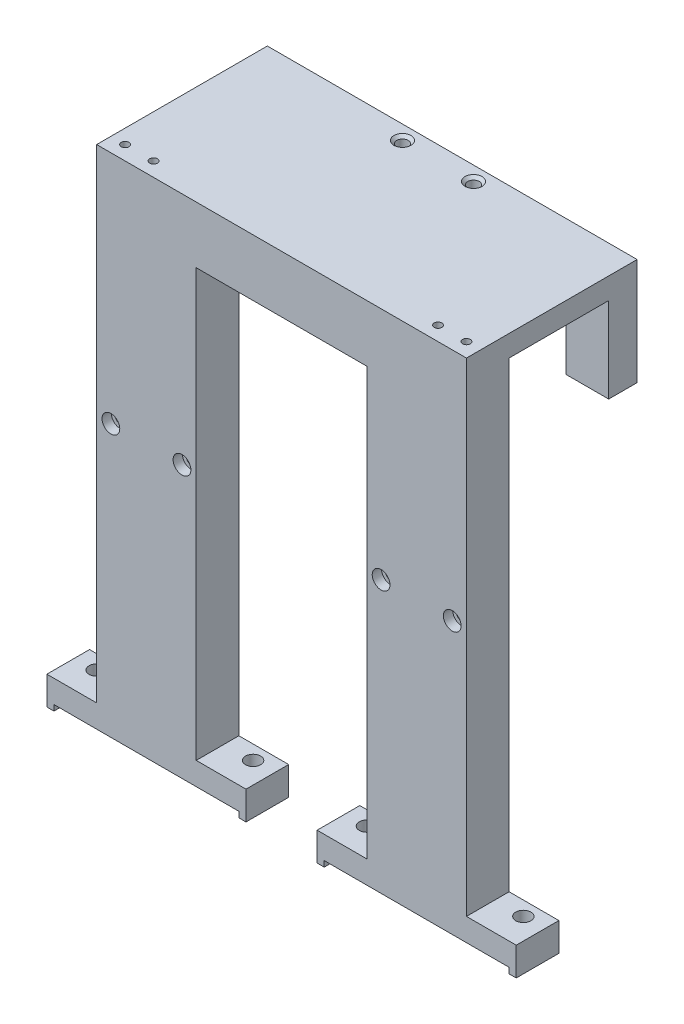
SolidWorks part; units mm, degrees
material "6061 Alloy"
ref_plane "Front Plane" through (0, 0, 0) normal (0, 0, 1) x (1, 0, 0)
ref_plane "Top Plane" through (0, 0, 0) normal (0, 1, 0) x (1, 0, 0)
ref_plane "Right Plane" through (0, 0, 0) normal (1, 0, 0) x (0, 0, -1)
sketch "Sketch1" plane through (0, 0, 0) normal (0, 0, 1) x (1, 0, 0)
  line L1 (-82.55, -114.3) -> (82.55, -114.3)
  line L2 (-82.55, -114.3) -> (-82.55, 114.3)
  line L3 (-82.55, 114.3) -> (82.55, 114.3)
  line L4 (82.55, -114.3) -> (82.55, 114.3)
  line L5 (-82.55, -114.3) -> (82.55, 114.3) construction
  line L6 (-82.55, 114.3) -> (82.55, -114.3) construction
  point P0 (0, 0)
  dimension "D1" = 228.6
  dimension "D2" = 165.1
extrude "Boss-Extrude1" add sketch "Sketch1" along normal blind 19.05
sketch "Sketch2" plane through (0, 0, 19.05) normal (0, 0, 1) x (1, 0, 0)
  line L0 (-82.55, -114.3) -> (82.55, -114.3) construction
  line L1 (-38.1, -114.3) -> (38.1, -114.3)
  line L2 (-38.1, -114.3) -> (-38.1, 88.9)
  line L3 (-38.1, 88.9) -> (38.1, 88.9)
  line L4 (38.1, -114.3) -> (38.1, 88.9)
  line L5 (-82.55, 114.3) -> (-82.55, -114.3) construction
  dimension "D1" = 203.2
  dimension "D2" = 76.2
  dimension "D3" = 44.45
extrude "Cut-Extrude1" cut sketch "Sketch2" against normal through all
sketch "Sketch3" plane through (0, 0, 0) normal (0, 0, -1) x (-1, 0, 0)
  line L0 (82.55, 114.3) -> (82.55, -114.3) construction
  line L1 (-82.55, 114.3) -> (82.55, 114.3)
  line L2 (-82.55, 114.3) -> (-82.55, 104.775)
  line L3 (-82.55, 104.775) -> (82.55, 104.775)
  line L4 (82.55, 114.3) -> (82.55, 104.775)
  dimension "D1" = 9.525
extrude "Boss-Extrude2" add sketch "Sketch3" along normal blind 57.15
sketch "Sketch4" plane through (0, 0, -57.15) normal (0, 0, -1) x (-1, 0, 0)
  line L7 (-82.55, 104.775) -> (-63.5, 104.775)
  line L8 (-82.55, 104.775) -> (-82.55, 66.675)
  line L9 (-82.55, 66.675) -> (-63.5, 66.675)
  line L10 (-63.5, 104.775) -> (-63.5, 66.675)
  dimension "D1" = 38.1
  dimension "D2" = 19.05
extrude "Boss-Extrude3" add sketch "Sketch4" against normal blind 12.7
mirror "Mirror1" about plane through (0, 0, 0) normal (1, 0, 0) of "Boss-Extrude3"
sketch "Sketch7" plane through (0, 0, 19.05) normal (0, 0, 1) x (1, 0, 0)
  line L0 (-82.55, -114.3) -> (-38.1, -114.3) construction
  line L1 (-104.775, -101.6) -> (-15.875, -101.6)
  line L2 (-104.775, -101.6) -> (-104.775, -114.3)
  line L3 (-104.775, -114.3) -> (-15.875, -114.3)
  line L4 (-15.875, -101.6) -> (-15.875, -114.3)
  line L5 (-104.775, -101.6) -> (-15.875, -114.3) construction
  line L6 (-104.775, -114.3) -> (-15.875, -101.6) construction
  line L7 (-82.55, 114.3) -> (-82.55, -114.3) construction
  point P0 (-60.325, -107.95)
  dimension "D1" = 0
  dimension "D2" = 88.9
  dimension "D3" = 22.225
  dimension "D4" = 12.7
extrude "Boss-Extrude4" add sketch "Sketch7" against normal blind 19.05
sketch "Sketch8" plane through (0, -114.3, 0) normal (0, -1, 0) x (-1, 0, 0)
  line L0 (104.775, -19.05) -> (15.875, -19.05) construction
  line L1 (101.6, 0) -> (19.05, 0)
  line L2 (101.6, 0) -> (101.6, -19.05)
  line L3 (101.6, -19.05) -> (19.05, -19.05)
  line L4 (19.05, 0) -> (19.05, -19.05)
  line L5 (101.6, 0) -> (19.05, -19.05) construction
  line L6 (101.6, -19.05) -> (19.05, 0) construction
  line L8 (104.775, 0) -> (104.775, -19.05) construction
  line L9 (15.875, 0) -> (15.875, -19.05) construction
  point P0 (60.325, -9.525)
  dimension "D1" = 19.05
  dimension "D2" = 3.175
  dimension "D3" = 3.175
extrude "Cut-Extrude4" cut sketch "Sketch8" against normal blind 2.54
mirror "Mirror3" about plane through (0, 0, 0) normal (1, 0, 0) of "Cut-Extrude4", "Boss-Extrude4"
hole_wizard "#8-32 Tapped Hole1" positions "Sketch11" profile "Sketch10" tap size "#8-32" standard "ANSI Inch"
sketch "Sketch11" plane through (0, 114.3, 0) normal (0, 1, 0) x (1, 0, 0)
  line L0 (-82.55, 0) -> (-82.55, -19.05) construction
  line L1 (-82.55, -19.05) -> (-82.55, 57.15) construction
  line L2 (82.55, 0) -> (82.55, -19.05) construction
  line L3 (82.55, -19.05) -> (82.55, 57.15) construction
  line L4 (82.55, -19.05) -> (-82.55, -19.05) construction
  point P0 (-76.2, -12.7)
  point P2 (-63.5, -12.7)
  point P4 (63.5, -12.7)
  point P6 (76.2, -12.7)
  dimension "D1" = 6.35
  dimension "D2" = 19.05
  dimension "D3" = 6.35
  dimension "D4" = 19.05
  dimension "D5" = 6.35
  dimension "D6" = 6.35
  dimension "D7" = 6.35
  dimension "D8" = 6.35
cosmetic thread "Hole Thread1" parameters "D1"=3.048, "D2"=4.1656
cosmetic thread "Hole Thread2" parameters "D1"=3.048, "D2"=4.1656
cosmetic thread "Hole Thread3" parameters "D1"=3.048, "D2"=4.1656
cosmetic thread "Hole Thread4" parameters "D1"=3.048, "D2"=4.1656
sketch "Sketch10" plane through (-76.2, 114.3, 12.7) normal (1, 0, 0) x (0, 0, 1)
  line L0 (0, 0) -> (0, 13.7378)
  line L1 (0, 13.7378) -> (1.7272, 12.7)
  line L2 (1.7272, 12.7) -> (1.7272, 0)
  line L5 (1.7272, 0) -> (0, 0)
  line L10 (0, 13.7378) -> (-1.7272, 12.7) construction
  line L11 (0, -6.35) -> (0, 107.95) construction
  dimension "Tap Drill Dia." = 3.4544
  dimension "Tap Drill Depth" = 12.7
  dimension "Drill Angle" = 118
hole_wizard "1/4 Clearance Hole1" positions "Sketch12" profile "Sketch13" hole size "1/4" standard "ANSI Inch" end condition up to next
sketch "Sketch12" plane through (0, -101.6, 0) normal (0, 1, 0) x (1, 0, 0)
  line L0 (-104.775, 0) -> (-104.775, -19.05) construction
  line L1 (-82.55, 0) -> (-104.775, 0) construction
  line L2 (-15.875, 0) -> (-38.1, 0) construction
  line L3 (-15.875, 0) -> (-15.875, -19.05) construction
  line L4 (15.875, 0) -> (15.875, -19.05) construction
  line L5 (15.875, 0) -> (38.1, 0) construction
  line L6 (82.55, 0) -> (104.775, 0) construction
  line L7 (104.775, 0) -> (104.775, -19.05) construction
  point P0 (-95.25, -6.35)
  point P2 (-25.4, -6.35)
  point P4 (25.4, -6.35)
  point P6 (95.25, -6.35)
  dimension "D1" = 9.525
  dimension "D2" = 6.35
  dimension "D3" = 6.35
  dimension "D4" = 9.525
  dimension "D5" = 9.525
  dimension "D6" = 6.35
  dimension "D7" = 6.35
  dimension "D8" = 9.525
sketch "Sketch13" plane through (-95.25, -101.6, 6.35) normal (1, 0, 0) x (0, 0, 1)
  line L0 (0, 0) -> (0, 10.16)
  line L1 (0, 10.16) -> (3.3782, 10.16)
  line L2 (3.3782, 10.16) -> (3.3782, 0)
  line L5 (3.3782, 0) -> (0, 0)
  line L11 (0, -6.35) -> (0, 107.95) construction
  dimension "Thru Hole Dia." = 6.7564
  dimension "Thru Hole Depth" = 10.16
hole_wizard "CBORE for #8 Socket Head Cap Screw1" positions "Sketch18" profile "Sketch19" counterbore size "#8" standard "ANSI Inch" end condition up to next
sketch "Sketch18" plane through (0, 0, 19.05) normal (0, 0, 1) x (1, 0, 0)
  line L0 (-82.55, 114.3) -> (-82.55, -101.6) construction
  line L1 (-38.1, 88.9) -> (-38.1, -101.6) construction
  line L2 (38.1, -101.6) -> (38.1, 88.9) construction
  line L3 (82.55, -101.6) -> (82.55, 114.3) construction
  point P0 (-76.2, 9.525)
  point P2 (-44.45, 9.525)
  point P4 (44.45, 9.525)
  point P6 (76.2, 9.525)
  dimension "D1" = 6.35
  dimension "D2" = 6.35
  dimension "D3" = 6.35
  dimension "D4" = 6.35
  dimension "D5" = 111.125
  dimension "D6" = 111.125
  dimension "D7" = 111.125
  dimension "D8" = 111.125
sketch "Sketch19" plane through (-76.2, 9.525, 19.05) normal (1, 0, 0) x (0, -1, 0)
  line L0 (0, 0) -> (0, 19.05)
  line L1 (0, 19.05) -> (2.2479, 19.05)
  line L3 (2.2479, 19.05) -> (2.2479, 4.1656)
  line L4 (2.2479, 4.1656) -> (3.9687, 4.1656)
  line L5 (3.9687, 4.1656) -> (3.9687, 0)
  line L7 (3.9687, 0) -> (0, 0)
  line L11 (0, -6.35) -> (0, 107.95) construction
  dimension "Thru Hole Dia." = 4.4958
  dimension "Thru Hole Depth" = 19.05
  dimension "C'Bore Dia." = 7.9375
  dimension "C'Bore Depth" = 4.1656
hole_wizard "1/4-20 Tapped Hole1" positions "Sketch20" profile "Sketch21" tap size "1/4-20" standard "ANSI Inch" end condition through all
sketch "Sketch20" plane through (0, 114.3, 0) normal (0, 1, 0) x (1, 0, 0)
  line L0 (-82.55, -19.05) -> (-82.55, 57.15) construction
  line L1 (82.55, -19.05) -> (82.55, 57.15) construction
  line L2 (-82.55, 57.15) -> (82.55, 57.15) construction
  point P0 (15.875, 50.8)
  point P2 (-15.875, 50.8)
  dimension "D1" = 66.675
  dimension "D2" = 66.675
  dimension "D3" = 6.35
  dimension "D4" = 6.35
sketch "Sketch21" plane through (15.875, 114.3, -50.8) normal (1, 0, 0) x (0, 0, 1)
  line L0 (0, 0) -> (0, 228.6)
  line L1 (0, 228.6) -> (2.5527, 228.6)
  line L2 (2.5527, 228.6) -> (2.5527, 1.2573)
  line L3 (2.5527, 1.2573) -> (3.81, 0)
  line L5 (3.81, 0) -> (0, 0)
  line L6 (-2.5527, 1.2573) -> (-3.81, 0) construction
  line L11 (0, -6.35) -> (0, 107.95) construction
  dimension "Thru Tap Drill Dia." = 5.1054
  dimension "Thru Tap Drill Depth" = 228.6
  dimension "Near C'Sink Dia." = 7.62
  dimension "Near C'Sink Angle" = 90
cosmetic thread "Hole Thread5" parameters "D2"=6.35
cosmetic thread "Hole Thread6" parameters "D2"=6.35
sketch "Sketch22" plane through (0, 0, -57.15) normal (0, 0, -1) x (-1, 0, 0)
  line L0 (-63.5, 104.775) -> (63.5, 104.775) construction
  line L1 (3.175, 98.425) -> (-3.175, 98.425)
  line L2 (3.175, 98.425) -> (3.175, 104.775)
  line L3 (3.175, 104.775) -> (-3.175, 104.775)
  line L4 (-3.175, 98.425) -> (-3.175, 104.775)
  line L5 (3.175, 98.425) -> (-3.175, 104.775) construction
  line L6 (3.175, 104.775) -> (-3.175, 98.425) construction
  point P0 (0, 101.6)
  dimension "D1" = 6.35
  dimension "D2" = 6.35
  dimension "D3" = 0
extrude "Boss-Extrude5" add sketch "Sketch22" along normal blind 3.175 from offset 7.9375 separate body offset against normal yes
sketch "Sketch23" plane through (0, 0, -52.3875) normal (0, 0, -1) x (-1, 0, 0)
  line L0 (-3.175, 98.425) -> (3.175, 98.425) construction
  line L1 (-3.175, 104.775) -> (-3.175, 98.425) construction
  circle A0 centre (0, 101.6) radius 1.5875
  dimension "D3" = 3.175
  dimension "D1" = 3.175
  dimension "D2" = 3.175
extrude "Cut-Extrude5" cut sketch "Sketch23" against normal up to next (3.175 mm away)
